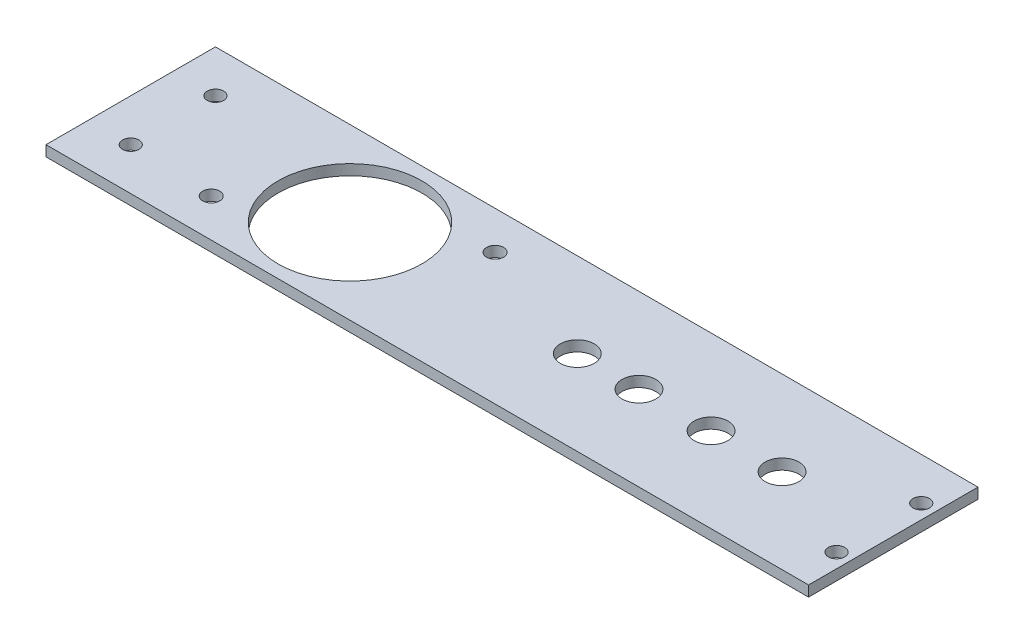
SolidWorks part; units mm, degrees
ref_plane "Front Plane" through (0, 0, 0) normal (0, 0, 1) x (1, 0, 0)
ref_plane "Top Plane" through (0, 0, 0) normal (0, 1, 0) x (1, 0, 0)
ref_plane "Right Plane" through (0, 0, 0) normal (1, 0, 0) x (0, 0, -1)
sketch "Sketch1" plane through (0, 0, 0) normal (0, 1, 0) x (1, 0, 0)
  line L1 (114.3, -25.4) -> (-114.3, -25.4)
  line L2 (114.3, -25.4) -> (114.3, 25.4)
  line L3 (114.3, 25.4) -> (-114.3, 25.4)
  line L4 (-114.3, -25.4) -> (-114.3, 25.4)
  line L5 (114.3, -25.4) -> (-114.3, 25.4) construction
  line L6 (114.3, 25.4) -> (-114.3, -25.4) construction
  point P0 (0, 0)
  dimension "D1" = 228.6
  dimension "D2" = 50.8
extrude "Boss-Extrude1" add sketch "Sketch1" along normal blind 3.175
hole_wizard "#10 (0.1935) Diameter Hole1" positions "Sketch2" profile "Sketch3" hole size "#10" standard "ANSI Inch" end condition through all
sketch "Sketch2" plane through (0, 3.175, 0) normal (0, 1, 0) x (1, 0, 0)
  line L0 (-101.6, 25.4) -> (-101.6, -25.4) construction
  line L1 (114.3, 25.4) -> (-114.3, 25.4) construction
  line L2 (-114.3, -25.4) -> (114.3, -25.4) construction
  line L4 (-114.3, 25.4) -> (-114.3, -25.4) construction
  line L5 (109.982, -25.4) -> (109.982, 25.4) construction
  line L7 (114.3, -25.4) -> (114.3, 25.4) construction
  point P11 (-101.6, -12.7)
  point P13 (-101.6, 12.7)
  point P23 (109.982, -12.7)
  point P25 (109.982, 12.7)
  dimension "D1" = 12.7
  dimension "D2" = 12.7
  dimension "D3" = 12.7
  dimension "D4" = 4.318
  dimension "D5" = 12.7
  dimension "D6" = 12.7
sketch "Sketch3" plane through (109.982, 3.175, -12.7) normal (1, 0, 0) x (0, 0, 1)
  line L0 (0, 0) -> (0, 3.175)
  line L1 (0, 3.175) -> (2.4574, 3.175)
  line L2 (2.4574, 3.175) -> (2.4574, 0)
  line L5 (2.4574, 0) -> (0, 0)
  line L11 (0, -6.35) -> (0, 107.95) construction
  dimension "Thru Hole Dia." = 4.9149
  dimension "Thru Hole Depth" = 3.175
hole_wizard "1/4-20 Tapped Hole1" positions "Sketch4" profile "Sketch5" tap size "1/4-20" standard "ANSI Inch" end condition through all
sketch "Sketch4" plane through (0, 3.175, 0) normal (0, 1, 0) x (1, 0, 0)
  line L0 (-114.3, 25.4) -> (-88.9, 25.4) construction
  line L1 (114.3, 25.4) -> (-114.3, 25.4) construction
  line L3 (-88.9, 25.4) -> (-88.9, -25.4) construction
  line L4 (-114.3, -25.4) -> (114.3, -25.4) construction
  line L6 (-88.9, 0) -> (-76.2, 0) construction
  line L7 (-76.2, -13.97) -> (-76.2, 0) construction
  line L9 (-76.2, 0) -> (-19.05, 0) construction
  line L10 (-19.05, 0) -> (-19.05, 13.97) construction
  point P42 (-19.05, 13.97)
  point P47 (-76.2, -13.97)
  dimension "D1" = 25.4
  dimension "D2" = 57.15
  dimension "D3" = 12.7
sketch "Sketch5" plane through (-76.2, 3.175, 13.97) normal (1, 0, 0) x (0, 0, 1)
  line L0 (0, 0) -> (0, 3.175)
  line L1 (0, 3.175) -> (2.5527, 3.175)
  line L2 (2.5527, 3.175) -> (2.5527, 0)
  line L5 (2.5527, 0) -> (0, 0)
  line L11 (0, -6.35) -> (0, 107.95) construction
  dimension "Thread Major Dia." = 5.1054
  dimension "Thru Tap Drill Depth" = 3.175
sketch "Sketch6" plane through (0, 3.175, 0) normal (0, 1, 0) x (1, 0, 0)
  line L0 (-114.3, 0) -> (114.3, 0) construction
  line L1 (-114.3, 25.4) -> (-114.3, -25.4) construction
  line L2 (114.3, -25.4) -> (114.3, 25.4) construction
  circle A0 centre (-48.5694, 0) radius 21.5734
  circle A1 centre (80.9561, 0) radius 5.08
  circle A2 centre (59.671, 0) radius 5.08
  circle A3 centre (38.056, 0) radius 5.08
  circle A4 centre (19.5759, 0) radius 5.08
  dimension "D1" = 10.16
extrude "Cut-Extrude1" cut sketch "Sketch6" against normal through all
